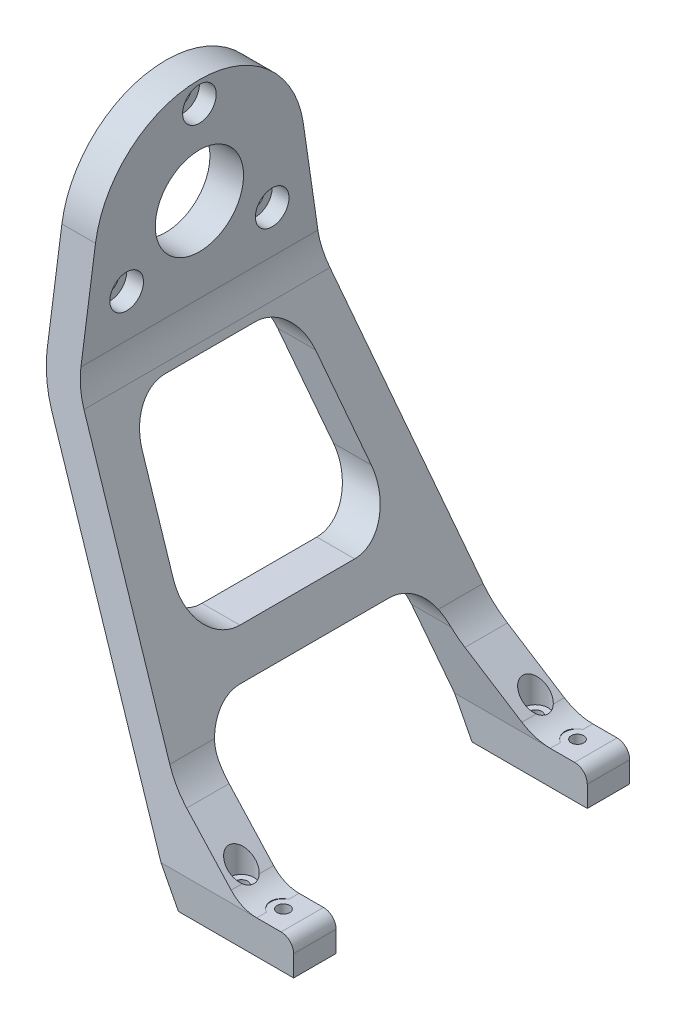
SolidWorks part; units mm, degrees
material "6061 合金"
ref_plane "前视基准面" through (0, 0, 0) normal (0, 0, 1) x (1, 0, 0)
ref_plane "上视基准面" through (0, 0, 0) normal (0, 1, 0) x (1, 0, 0)
ref_plane "右视基准面" through (0, 0, 0) normal (1, 0, 0) x (0, 0, -1)
sketch "草图1" plane through (0, 0, 0) normal (0, 0, 1) x (1, 0, 0)
  line L0 (0, 50) -> (0, 4.8715)
  line L1 (2.2402, -4.3258) -> (41.43, -80)
  line L2 (41.43, -80) -> (66.43, -80)
  arc A0 (2.2402, -4.3258) -> (0, 4.8715) centre (20, 4.8715) cw
  point P7 (0, 0)
  dimension "D5" = 20
  dimension "D1" = 80
  dimension "D2" = 41.43
  dimension "D3" = 50
  dimension "D4" = 25
extrude "拉伸-薄壁1" add sketch "草图1" along normal blind 80 thin thin type mid plane wall 8
sketch "草图8" plane through (0, 0, 0) normal (0, 0, -1) x (-1, 0, 0)
  line L0 (-53.9969, -76) -> (-36.0752, -60.9619)
  line L1 (-43.8631, -76) -> (-66.43, -76) construction
  line L2 (-5.7922, -2.4864) -> (-43.8631, -76) construction
  line L3 (-36.0752, -60.9619) -> (-43.8631, -76)
  line L4 (-43.8631, -76) -> (-53.9969, -76)
  dimension "D1" = 40
  dimension "D2" = 15
extrude "凸台-拉伸1" add sketch "草图8" against normal through all
sketch "草图2" plane through (-4, 0, 0) normal (-1, 0, 0) x (0, 0, 1)
  line L0 (80, 50) -> (0, 50) construction
  line L1 (15.2619, 28.6092) -> (0, -76)
  line L2 (0, -6.1653) -> (0, -84) construction
  line L3 (40, 85.5078) -> (40, -146.0129) construction
  line L4 (80, -84) -> (0, -84) construction
  line L5 (64.7381, 28.6092) -> (80, -76)
  line L9 (0, 50) -> (0, -76)
  line L10 (80, -76) -> (80, 50)
  line L11 (80, 50) -> (0, 50)
  arc A0 (15.2619, 28.6092) -> (64.7381, 28.6092) centre (40, 25) cw
  point P6 (40, 50)
  line M3 (0, 50) -> (0, 4.8715)
  line M5 (80, 4.8715) -> (80, 50)
  line M6 (80, 50) -> (0, 50)
  dimension "D1" = 25
  dimension "D2" = 8
extrude "切除-拉伸1" cut sketch "草图2" against normal through all contours L1 A0 L11 M3 | L1 | L5 | A0 L5 M6 M5 region at (-4, 10.8244, 72.6384) region at (-4, 10.8244, 7.3616)
fillet "圆角4" radius 10 1 edges at (53.9969, -76, 40)
fillet "圆角5" radius 20 1 edges at (36.0752, -60.9619, 40)
sketch "草图3" plane through (0, -84, 0) normal (0, -1, 0) x (1, 0, 0)
  line L0 (-21.9643, 40) -> (81.8416, 40) construction
  line L1 (66.43, 80) -> (66.43, 0) construction
  line L2 (38.9969, 80) -> (38.9969, 0) construction
  line L3 (38.9969, 80) -> (66.43, 80) construction
  circle A0 centre (48.9969, 75) radius 1.5
  circle A1 centre (58.9969, 75) radius 1.5
  circle A2 centre (58.9969, 5) radius 1.5
  circle A3 centre (48.9969, 5) radius 1.5
  point P9 (66.43, 40)
  dimension "D4" = 3
  dimension "D1" = 10
  dimension "D2" = 10
  dimension "D3" = 5
extrude "切除-拉伸2" cut sketch "草图3" against normal through all
sketch "草图5" plane through (-4, 0, 0) normal (-1, 0, 0) x (0, 0, 1)
  line L0 (10.1059, -84) -> (10.1059, -76)
  line L1 (80, -84) -> (0, -84) construction
  line L2 (10.1059, -76) -> (13.6073, -52)
  line L3 (20.6103, -4) -> (59.3897, -4)
  line L4 (59.3897, -4) -> (65.2255, -44)
  line L5 (69.8941, -76) -> (69.8941, -84)
  line L6 (69.8941, -84) -> (10.1059, -84)
  line L7 (40, 64.2186) -> (40, -117.6272) construction
  line L8 (0, -76) -> (10.1885, -6.1653) construction
  line L9 (14.7745, -44) -> (65.2255, -44)
  line L10 (13.6073, -52) -> (66.3927, -52)
  line L11 (66.3927, -52) -> (69.8941, -76)
  line L12 (14.7745, -44) -> (20.6103, -4)
  dimension "D1" = 10
  dimension "D2" = 80
  dimension "D3" = 8
  dimension "D4" = 8
  dimension "D5" = 40
extrude "切除-拉伸4" cut sketch "草图5" against normal through all
sketch "草图6" plane through (4, 0, 0) normal (1, 0, 0) x (0, 0, -1)
  circle A0 centre (-40, 25) radius 10.5
  circle A1 centre (-40, 45) radius 2
  circle A2 centre (-22.6795, 15) radius 2
  circle A3 centre (-57.3205, 15) radius 2
  point P11 (-40, 25)
  dimension "D1" = 21
  dimension "D3" = 4
  dimension "D2" = 20
  dimension "D4" = 3
extrude "切除-拉伸5" cut sketch "草图6" against normal through all
sketch "草图7" plane through (4, 0, 0) normal (1, 0, 0) x (0, 0, -1)
  circle A0 centre (-40, 45) radius 4
  circle A1 centre (-22.6795, 15) radius 4
  circle A2 centre (-57.3205, 15) radius 4
  dimension "D1" = 8
extrude "切除-拉伸6" cut sketch "草图7" against normal blind 4
fillet "圆角2" radius 10 6 edges at (2.138, -4, 59.3897) (26.9295, -52, 13.6073) (26.9295, -52, 66.3927) (22.7865, -44, 65.2255) (22.7865, -44, 14.7745) (2.138, -4, 20.6103)
fillet "圆角3" radius 3 2 edges at (66.43, -76, 5.0529) (66.43, -76, 74.9471)
ref_plane "基准面1" through (0, -66, 0) normal (0, 1, 0) x (1, 0, 0)
sketch "草图9" plane through (0, -66, 0) normal (0, 1, 0) x (1, 0, 0)
  circle A0 centre (48.9969, -75) radius 3
  circle A1 centre (58.9969, -75) radius 3
  circle A2 centre (58.9969, -5) radius 3
  circle A3 centre (48.9969, -5) radius 3
  dimension "D1" = 6
  dimension "D2" = 6
  dimension "D3" = 6
  dimension "D4" = 6
extrude "切除-拉伸7" cut sketch "草图9" against normal blind 10
